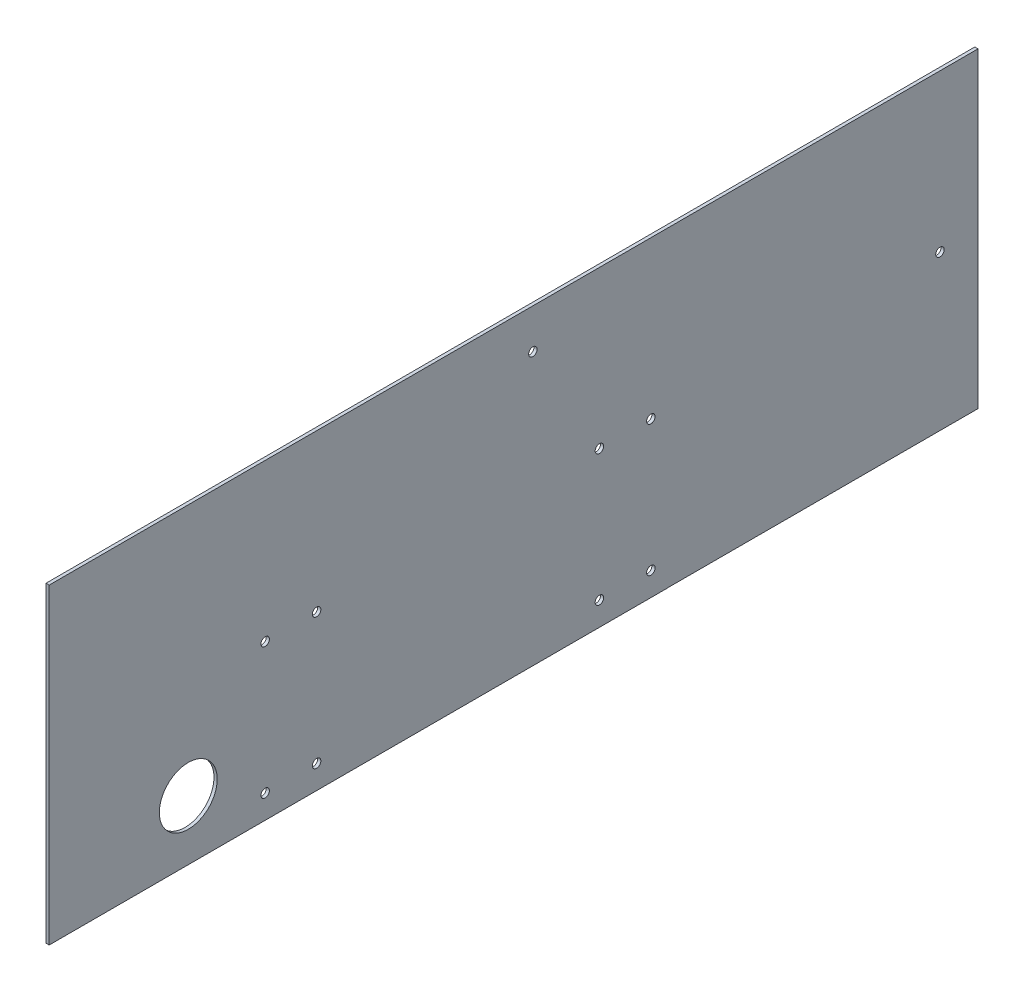
SolidWorks part; units mm, degrees
ref_plane "Front Plane" through (0, 0, 0) normal (0, 0, 1) x (1, 0, 0)
ref_plane "Top Plane" through (0, 0, 0) normal (0, 1, 0) x (1, 0, 0)
ref_plane "Right Plane" through (0, 0, 0) normal (1, 0, 0) x (0, 0, -1)
sketch "Sketch1" plane through (0, 0, 0) normal (1, 0, 0) x (0, 0, -1)
  line L1 (-152.4, -58.42) -> (152.4, -58.42)
  line L2 (-152.4, -58.42) -> (-152.4, 58.42)
  line L3 (-152.4, 58.42) -> (152.4, 58.42)
  line L4 (152.4, -58.42) -> (152.4, 58.42)
  line L5 (-152.4, -58.42) -> (152.4, 58.42) construction
  line L6 (-152.4, 58.42) -> (152.4, -58.42) construction
  point P0 (0, 0)
  dimension "D1" = 116.84
  dimension "D2" = 304.8
extrude "Boss-Extrude1" add sketch "Sketch1" along normal blind 1.5875
sketch "Sketch2" plane through (1.5875, 0, 0) normal (1, 0, 0) x (0, 0, -1)
  line L0 (-152.4, -58.42) -> (-45.72, -58.42)
  line L1 (-152.4, -58.42) -> (152.4, -58.42) construction
  line L2 (-45.72, -58.42) -> (-45.72, -46.736)
  line L3 (-45.72, -46.736) -> (-20.32, -46.736)
  line L4 (-20.32, 18.034) -> (-20.32, -46.736)
  circle A0 centre (-45.72, -46.736) radius 2.0955
  circle A1 centre (-20.32, -46.736) radius 2.0955
  circle A2 centre (144.78, -46.736) radius 2.0955
  circle A3 centre (119.38, -46.736) radius 2.0955
  circle A4 centre (144.78, 18.034) radius 2.0955
  circle A5 centre (119.38, 18.034) radius 2.0955
  circle A6 centre (-20.32, 18.034) radius 2.0955
  circle A7 centre (-45.72, 18.034) radius 2.0955
  dimension "D4" = 4.191
  dimension "D5" = 4.191
  dimension "D1" = 106.68
  dimension "D2" = 11.684
  dimension "D3" = 25.4
  dimension "D6" = 2
  dimension "D7" = 2
extrude "Cut-Extrude1" cut sketch "Sketch2" against normal up to surface (1.5875 mm away) contours L3 A0 L2 | L2 A0 L3 | A1 | A2 | A3 | A7 | A6 | A5 | A4 | L4 A1 L3 region at (1.5875, -46.4395, 46.0165) region at (1.5875, 19.4738, 21.7598) region at (1.5875, -45.8466, 21.2094) region at (1.5875, -47.0325, 20.0235) region at (1.5875, -47.6254, 44.8306) region at (1.5875, -46.736, -144.78) region at (1.5875, -46.736, -119.38) region at (1.5875, 18.034, -144.78) region at (1.5875, 18.034, -119.38) region at (1.5875, 18.034, 45.72) up to face at (0, 0, 0)
sketch "Sketch3" plane through (0, 0, 0) normal (-1, 0, 0) x (0, 0, 1)
  line L0 (97.9932, -28.956) -> (152.4, -28.956)
  line L1 (152.4, 58.42) -> (152.4, -58.42) construction
  line L2 (152.4, -28.956) -> (83.7057, -28.956)
  line L3 (83.7057, -43.2435) -> (83.7057, -58.42)
  line L4 (152.4, -58.42) -> (-152.4, -58.42) construction
  circle A0 centre (83.7057, -28.956) radius 14.2875
  dimension "D3" = 28.575
  dimension "D1" = 54.4068
  dimension "D2" = 68.6943
extrude "Cut-Extrude2" cut sketch "Sketch3" against normal blind 3.175 contours A0
sketch "Sketch4" plane through (0, 0, 0) normal (-1, 0, 0) x (0, 0, 1)
  line L2 (152.4, 58.42) -> (-152.4, 58.42)
  line L3 (152.4, 58.42) -> (152.4, 95.5675)
  line L4 (152.4, 95.5675) -> (-152.4, 95.5675)
  line L5 (-152.4, 58.42) -> (-152.4, 95.5675)
  line L7 (-152.4, 95.5675) -> (-306.3875, 95.5675)
  line L8 (-152.4, 95.5675) -> (-152.4, -58.3565)
  line L9 (-152.4, -58.3565) -> (-306.3875, -58.3565)
  line L10 (-306.3875, 95.5675) -> (-306.3875, -58.3565)
  line M10 (-152.4, 58.42) -> (-152.4, -58.42)
  line M13 (152.4, 58.42) -> (-152.4, 58.42)
  dimension "D1" = 37.1475
  dimension "D2" = 153.924
  dimension "D3" = 153.9875
extrude "Boss-Extrude2" add sketch "Sketch4" against normal up to surface (1.5875 mm away) contours L7 L10 L9 L5 M10 | L5 L3 L4 M13 region at (0, 76.9937, 0) region at (0, 18.6055, -229.3937) up to face at (1.5875, -28.956, 97.9932)
sketch "Sketch5" plane through (0, 0, 0) normal (-1, 0, 0) x (0, 0, 1)
  line L0 (-306.3875, 95.5675) -> (-287.5915, 95.5675)
  line L1 (152.4, 95.5675) -> (-306.3875, 95.5675) construction
  line L2 (-144.78, 18.034) -> (-287.5915, 18.034)
  circle A1 centre (-287.5915, 18.034) radius 2.0955
  dimension "D2" = 4.191
  dimension "D1" = 18.796
extrude "Cut-Extrude3" cut sketch "Sketch5" against normal up to surface (1.5875 mm away) contours A1 region at (0, 18.034, -289.6277) up to face at (1.5875, -7.0697, -102.1292)
sketch "Sketch8" plane through (0, 0, 0) normal (-1, 0, 0) x (0, 0, 1)
  line L0 (-119.38, 18.034) -> (-119.38, 75.9366)
  line L1 (-119.38, 75.9366) -> (-86.51, 75.9366)
  circle A0 centre (-86.51, 75.9366) radius 2.0955
  circle A4 centre (20.32, 18.034) radius 2.0955 construction
  dimension "D1" = 57.9026
  dimension "D2" = 32.87
extrude "Cut-Extrude4" cut sketch "Sketch8" against normal up to surface (1.5875 mm away) contours A0 region at (0, 73.9003, -86.51) up to face at (1.5875, 18.034, -285.496)
